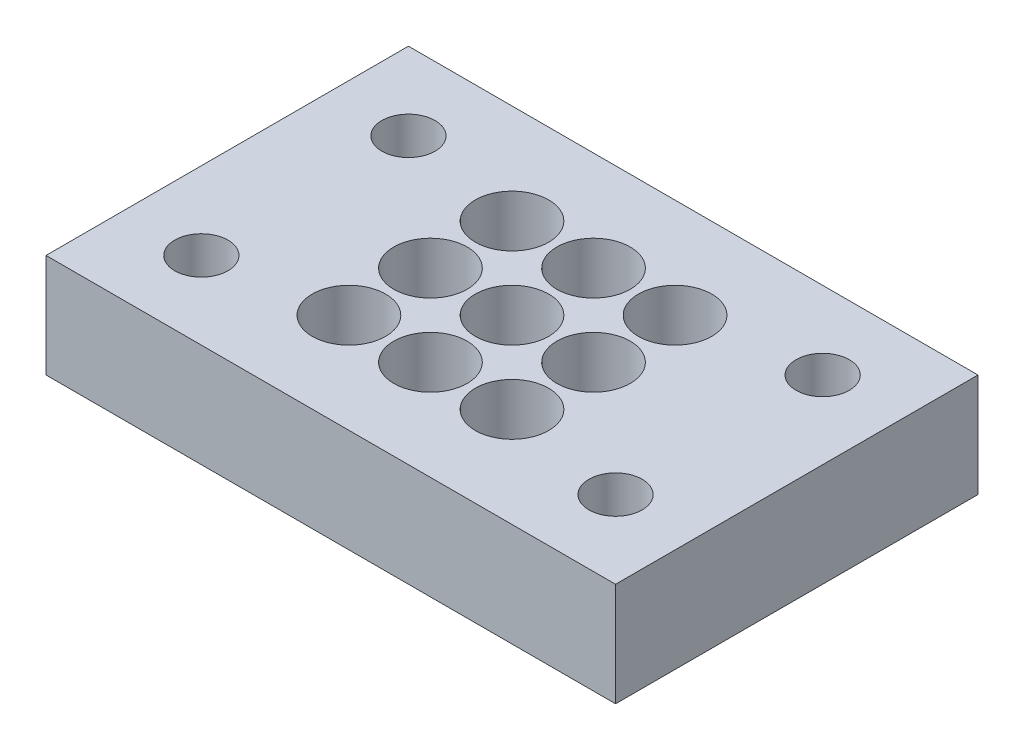
SolidWorks part; units mm, degrees
ref_plane "Front Plane" through (0, 0, 0) normal (0, 0, 1) x (1, 0, 0)
ref_plane "Top Plane" through (0, 0, 0) normal (0, 1, 0) x (1, 0, 0)
ref_plane "Right Plane" through (0, 0, 0) normal (1, 0, 0) x (0, 0, -1)
sketch "Sketch1" plane through (0, 0, 0) normal (0, 1, 0) x (1, 0, 0)
  line L0 (9.525, 34.925) -> (0, 34.925) construction
  line L1 (0, 0) -> (69.85, 0)
  line L2 (0, 0) -> (0, 44.45)
  line L3 (0, 44.45) -> (69.85, 44.45)
  line L4 (69.85, 0) -> (69.85, 44.45)
  line L5 (9.525, 34.925) -> (60.325, 34.925) construction
  line L6 (9.525, 34.925) -> (9.525, 9.525) construction
  line L7 (9.525, 9.525) -> (60.325, 9.525) construction
  line L8 (60.325, 34.925) -> (60.325, 9.525) construction
  line L9 (9.525, 34.925) -> (9.525, 44.45) construction
  circle A0 centre (9.525, 34.925) radius 3.2639
  circle A1 centre (60.325, 34.925) radius 3.2639
  circle A2 centre (9.525, 9.525) radius 3.2639
  circle A3 centre (60.325, 9.525) radius 3.2639
  circle A4 centre (34.925, 22.225) radius 4.5
  circle A5 centre (44.925, 22.225) radius 4.5
  circle A6 centre (44.925, 32.225) radius 4.5
  circle A7 centre (34.925, 32.225) radius 4.5
  circle A8 centre (24.925, 22.225) radius 4.5
  circle A9 centre (24.925, 32.225) radius 4.5
  circle A10 centre (34.925, 32.225) radius 4.5
  circle A11 centre (44.925, 22.225) radius 4.5
  circle A12 centre (44.925, 12.225) radius 4.5
  circle A13 centre (34.925, 12.225) radius 4.5
  circle A14 centre (24.925, 22.225) radius 4.5
  circle A15 centre (24.925, 12.225) radius 4.5
  circle A16 centre (34.925, 12.225) radius 4.5
  point P13 (34.925, 34.925)
  point P14 (34.925, 44.45)
  point P20 (69.85, 22.225)
  dimension "D5" = 6.5278
  dimension "D6" = 9
  dimension "D1" = 69.85
  dimension "D2" = 44.45
  dimension "D3" = 50.8
  dimension "D4" = 25.4
  dimension "D15" = 10
  dimension "D16" = 10
  dimension "D17" = 10
  dimension "D18" = 10
  dimension "D19" = 10
  dimension "D20" = 10
  dimension "D21" = 10
  dimension "D22" = 10
  dimension "D7" = 2
  dimension "D8" = 2
  dimension "D9" = 2
  dimension "D10" = 2
  dimension "D11" = 2
  dimension "D12" = 2
  dimension "D13" = 2
  dimension "D14" = 2
extrude "Boss-Extrude1" add sketch "Sketch1" along normal blind 12.7 contours L1 L4 L3 L2 A15 A13 A12 A9 A8 A7 A6 A5 A4 A3 A2 A1 A0 region at (0.8279, 0, -22.225)
equation "\"o\"= 10mm"
equation "\"P\"= 10"
